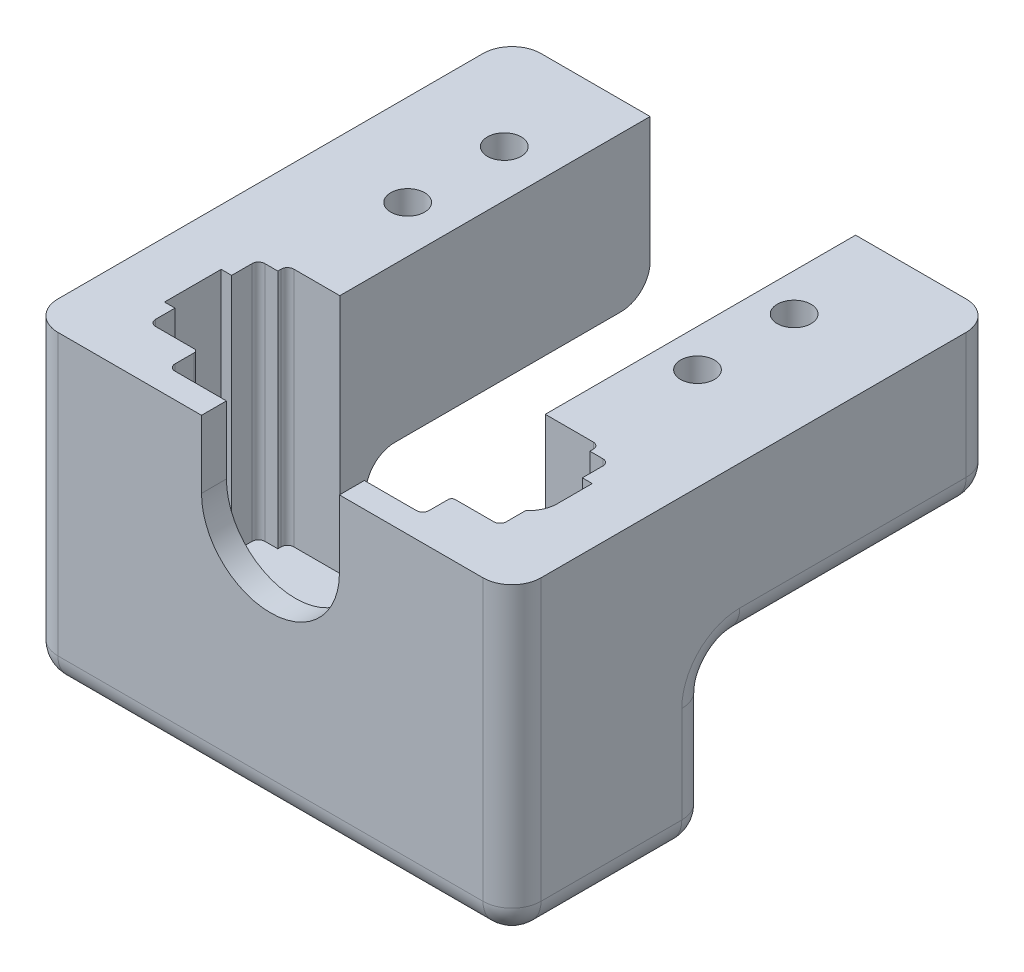
SolidWorks part; units mm, degrees
ref_plane "前视基准面" through (0, 0, 0) normal (0, 0, 1) x (1, 0, 0)
ref_plane "上视基准面" through (0, 0, 0) normal (0, 1, 0) x (1, 0, 0)
ref_plane "右视基准面" through (0, 0, 0) normal (1, 0, 0) x (0, 0, -1)
sketch "草图1" plane through (0, 0, 0) normal (0, 1, 0) x (1, 0, 0)
  line L1 (-25, -25) -> (25, -25)
  line L2 (-25, -25) -> (-25, 25)
  line L3 (-25, 25) -> (-11.2619, 25)
  line L4 (25, -25) -> (25, 25)
  line L5 (-6.2707, -6.2707) -> (25, 25) construction
  line L6 (-25, 25) -> (0, 0) construction
  line L7 (-18.1805, -10.8988) -> (-19.2049, -10.8988)
  line L10 (-15.4695, -7.1202) -> (-14.2003, -7.1202)
  line L11 (16.1805, -7.7702) -> (16.1805, -8.1202)
  line L12 (16.1805, -8.1202) -> (17.5305, -8.1202)
  line L13 (18.1805, -8.7702) -> (18.1805, -10.8988)
  line L14 (17.5305, -19.4202) -> (13.5305, -19.4202)
  line L24 (13.1805, -21.7702) -> (13.1805, -19.7702)
  line L25 (12.5305, -22.4202) -> (-12.4695, -22.4202)
  line L26 (-13.1195, -21.7702) -> (-13.1195, -19.7702)
  line L27 (-13.4695, -19.4202) -> (-17.4695, -19.4202)
  line L28 (-18.1195, -18.7702) -> (-18.1195, -16.7665)
  line L29 (-17.4695, -8.1202) -> (-16.1195, -8.1202)
  line L30 (-16.1195, -7.7702) -> (-16.1195, -8.1202)
  line L31 (18.1805, -10.8988) -> (19.2049, -10.8988)
  line L32 (19.2049, -10.8988) -> (19.2049, -16.7665)
  line L33 (19.2049, -16.7665) -> (18.1805, -16.7665)
  line L35 (0, -35.6784) -> (0, 5.6108) construction
  line L36 (-19.2049, -10.8988) -> (-19.2049, -16.7665)
  line L37 (-19.2049, -16.7665) -> (-18.1805, -16.7665)
  line L39 (-18.1805, -10.8988) -> (-18.1195, -10.8988)
  line L40 (-18.1805, -16.7665) -> (-18.1195, -16.7665)
  line L41 (18.1805, -16.7665) -> (18.1805, -18.7702)
  line L42 (-18.1195, -10.8988) -> (-18.1195, -8.7702)
  line L49 (7.1202, -7.1202) -> (25, -25) construction
  line L51 (12.5305, -7.1202) -> (15.5305, -7.1202)
  line L52 (12.5305, 25) -> (25, 25)
  line L53 (-14.2003, -7.1202) -> (-10.7032, -7.1202)
  line L54 (-10.7032, -7.1202) -> (-10.7032, 25)
  line L55 (-10.7032, 25) -> (-11.2619, 25)
  line L56 (12.5305, -7.1202) -> (10.5649, -7.1202)
  line L57 (10.5649, -7.1202) -> (10.5649, 25)
  line L58 (10.5649, 25) -> (12.5305, 25)
  arc A2 (16.1805, -7.7702) -> (15.5305, -7.1202) centre (15.5305, -7.7702) ccw
  arc A3 (18.1805, -8.7702) -> (17.5305, -8.1202) centre (17.5305, -8.7702) ccw
  arc A4 (17.5305, -19.4202) -> (18.1805, -18.7702) centre (17.5305, -18.7702) ccw
  arc A5 (13.5305, -19.4202) -> (13.1805, -19.7702) centre (13.5305, -19.7702) ccw
  arc A6 (12.5305, -22.4202) -> (13.1805, -21.7702) centre (12.5305, -21.7702) ccw
  arc A7 (-13.1195, -21.7702) -> (-12.4695, -22.4202) centre (-12.4695, -21.7702) ccw
  arc A8 (-13.1195, -19.7702) -> (-13.4695, -19.4202) centre (-13.4695, -19.7702) ccw
  arc A18 (-18.1195, -18.7702) -> (-17.4695, -19.4202) centre (-17.4695, -18.7702) ccw
  arc A19 (-17.4695, -8.1202) -> (-18.1195, -8.7702) centre (-17.4695, -8.7702) ccw
  arc A20 (-15.4695, -7.1202) -> (-16.1195, -7.7702) centre (-15.4695, -7.7702) ccw
  point P0 (0, 0)
  dimension "D1" = 50
  dimension "D2" = 50
extrude "凸台-拉伸1" add sketch "草图1" along normal blind 25
sketch "草图2" plane through (0, 0, 25) normal (0, 0, 1) x (1, 0, 0)
  line L4 (-25, 0) -> (25, 0)
  line L5 (25, 0) -> (25, 25)
  line L6 (25, 25) -> (-25, 25)
  line L7 (-25, 25) -> (-25, 0)
  line L8 (-25, 0) -> (25, 0)
  line L9 (25, 0) -> (25, 25)
  line L10 (25, 25) -> (-25, 25)
  line L11 (-25, 25) -> (-25, 0)
  arc A0 (-7.139, 25) -> (7.139, 25) centre (0, 25) ccw
  dimension "D1" = 0
extrude "切除-拉伸1" cut sketch "草图2" against normal blind 10 contours L10 A0 region at (0, 21.9701, 25)
sketch "草图5" plane through (0, 0, 0) normal (0, -1, 0) x (1, 0, 0)
  line L1 (-20.889, 4.4234) -> (20.889, 4.4234)
  line L2 (-20.889, 4.4234) -> (-20.889, 23.3182)
  line L3 (-20.889, 23.3182) -> (20.889, 23.3182)
  line L4 (20.889, 4.4234) -> (20.889, 23.3182)
  line L5 (-20.889, 4.4234) -> (20.889, 23.3182) construction
  line L6 (-20.889, 23.3182) -> (20.889, 4.4234) construction
  point P0 (0, 13.8708)
extrude "凸台-拉伸4" add sketch "草图5" against normal blind 7.1
sketch "草图6" plane through (0, 0, 0) normal (0, -1, 0) x (1, 0, 0)
  circle A4 centre (-15.551, -4.753) radius 1.75
  circle A5 centre (-15.551, -14.753) radius 1.75
  circle A6 centre (14.449, -4.753) radius 1.75
  circle A7 centre (14.449, -14.753) radius 1.75
  dimension "D1" = 3.5
  dimension "D2" = 3.5
  dimension "D3" = 3.5
  dimension "D4" = 3.5
extrude "切除-拉伸2" cut sketch "草图6" against normal through all
sketch "草图7" plane through (0, 0, 0) normal (0, -1, 0) x (1, 0, 0)
  line L0 (-10.7032, 4.4234) -> (-25, 4.4234)
  line L1 (-25, -25) -> (-25, 25) construction
  line L2 (-25, 4.4234) -> (-25, -26.3625)
  line L3 (-25, -26.3625) -> (26.9277, -26.3625)
  line L4 (26.9277, -26.3625) -> (26.9277, 4.4234)
  line L5 (26.9277, 4.4234) -> (-10.7032, 4.4234)
extrude "切除-拉伸3" cut sketch "草图7" against normal blind 16
fillet "圆角1" radius 3 13 edges at (25, 16, -10.2883) (-25, 16, -10.2883) (0, 0, 25) (25, 0, 14.7117) (0, 0, 4.4234) (-25, 0, 14.7117) (25, 12.5, 25) (19.2049, 16.05, 16.7665) (-25, 12.5, 25) (25, 8, 4.4234) (17.7824, 16, 4.4234) (-17.8516, 16, 4.4234) (-25, 8, 4.4234)
fillet "圆角3" radius 3 6 edges at (-16.3516, 16, -25) (-24.1213, 16.8787, -25) (16.2824, 16, -25) (24.1213, 16.8787, -25) (-25, 22, -25) (25, 22, -25)
sketch "草图8" plane through (0, 25, 0) normal (0, 1, 0) x (1, 0, 0)
  line L15 (25, -22) -> (25, 22)
  line L16 (22, 25) -> (10.5649, 25)
  line L17 (10.5649, 25) -> (10.5649, -7.1202)
  line L18 (10.5649, -7.1202) -> (15.5305, -7.1202)
  line L19 (16.1805, -7.7702) -> (16.1805, -8.1202)
  line L20 (16.1805, -8.1202) -> (17.5305, -8.1202)
  line L21 (18.1805, -8.7702) -> (18.1805, -10.8988)
  line L22 (18.1805, -10.8988) -> (19.2049, -10.8988)
  line L23 (19.2049, -10.8988) -> (19.2049, -14.5089)
  line L24 (18.1805, -16.7665) -> (18.1805, -18.7702)
  line L25 (17.5305, -19.4202) -> (13.5305, -19.4202)
  line L26 (13.1805, -19.7702) -> (13.1805, -21.7702)
  line L27 (12.5305, -22.4202) -> (7.139, -22.4202)
  line L28 (7.139, -22.4202) -> (7.139, -25)
  line L29 (7.139, -25) -> (22, -25)
  line L30 (25, -22) -> (25, 22)
  line L31 (22, 25) -> (10.5649, 25)
  line L32 (10.5649, 25) -> (10.5649, -7.1202)
  line L33 (10.5649, -7.1202) -> (15.5305, -7.1202)
  line L34 (16.1805, -7.7702) -> (16.1805, -8.1202)
  line L35 (16.1805, -8.1202) -> (17.5305, -8.1202)
  line L36 (18.1805, -8.7702) -> (18.1805, -10.8988)
  line L37 (18.1805, -10.8988) -> (19.2049, -10.8988)
  line L38 (19.2049, -10.8988) -> (19.2049, -14.5089)
  line L39 (18.1805, -16.7665) -> (18.1805, -18.7702)
  line L40 (17.5305, -19.4202) -> (13.5305, -19.4202)
  line L41 (13.1805, -19.7702) -> (13.1805, -21.7702)
  line L42 (12.5305, -22.4202) -> (7.139, -22.4202)
  line L43 (7.139, -22.4202) -> (7.139, -25)
  line L44 (7.139, -25) -> (22, -25)
  line L46 (-10.7032, 25) -> (-22, 25)
  line L47 (-25, 22) -> (-25, -22)
  line L48 (-22, -25) -> (-7.139, -25)
  line L49 (-7.139, -25) -> (-7.139, -22.4202)
  line L50 (-7.139, -22.4202) -> (-12.4695, -22.4202)
  line L51 (-13.1195, -21.7702) -> (-13.1195, -19.7702)
  line L52 (-13.4695, -19.4202) -> (-17.4695, -19.4202)
  line L53 (-18.1195, -18.7702) -> (-18.1195, -16.7665)
  line L54 (-18.1195, -16.7665) -> (-19.2049, -16.7665)
  line L55 (-19.2049, -16.7665) -> (-19.2049, -10.8988)
  line L56 (-19.2049, -10.8988) -> (-18.1195, -10.8988)
  line L57 (-18.1195, -10.8988) -> (-18.1195, -8.7702)
  line L58 (-17.4695, -8.1202) -> (-16.1195, -8.1202)
  line L59 (-16.1195, -8.1202) -> (-16.1195, -7.7702)
  line L60 (-15.4695, -7.1202) -> (-10.7032, -7.1202)
  line L61 (-10.7032, -7.1202) -> (-10.7032, 25)
  line L62 (-10.7032, 25) -> (-22, 25)
  line L63 (-25, 22) -> (-25, -22)
  line L64 (-22, -25) -> (-7.139, -25)
  line L65 (-7.139, -25) -> (-7.139, -22.4202)
  line L66 (-7.139, -22.4202) -> (-12.4695, -22.4202)
  line L67 (-13.1195, -21.7702) -> (-13.1195, -19.7702)
  line L68 (-13.4695, -19.4202) -> (-17.4695, -19.4202)
  line L69 (-18.1195, -18.7702) -> (-18.1195, -16.7665)
  line L70 (-18.1195, -16.7665) -> (-19.2049, -16.7665)
  line L71 (-19.2049, -16.7665) -> (-19.2049, -10.8988)
  line L72 (-19.2049, -10.8988) -> (-18.1195, -10.8988)
  line L73 (-18.1195, -10.8988) -> (-18.1195, -8.7702)
  line L74 (-17.4695, -8.1202) -> (-16.1195, -8.1202)
  line L75 (-16.1195, -8.1202) -> (-16.1195, -7.7702)
  line L76 (-15.4695, -7.1202) -> (-10.7032, -7.1202)
  line L77 (-10.7032, -7.1202) -> (-10.7032, 25)
  arc A7 (-22, 25) -> (-25, 22) centre (-22, 22) ccw
  arc A8 (25, 22) -> (22, 25) centre (22, 22) ccw
  arc A9 (16.1805, -7.7702) -> (15.5305, -7.1202) centre (15.5305, -7.7702) ccw
  arc A10 (18.1805, -8.7702) -> (17.5305, -8.1202) centre (17.5305, -8.7702) ccw
  arc A11 (18.1805, -16.7665) -> (19.2049, -14.5089) centre (16.2049, -14.5089) ccw
  arc A12 (17.5305, -19.4202) -> (18.1805, -18.7702) centre (17.5305, -18.7702) ccw
  arc A13 (13.5305, -19.4202) -> (13.1805, -19.7702) centre (13.5305, -19.7702) ccw
  arc A14 (12.5305, -22.4202) -> (13.1805, -21.7702) centre (12.5305, -21.7702) ccw
  arc A15 (22, -25) -> (25, -22) centre (22, -22) ccw
  arc A16 (25, 22) -> (22, 25) centre (22, 22) ccw
  arc A17 (16.1805, -7.7702) -> (15.5305, -7.1202) centre (15.5305, -7.7702) ccw
  arc A18 (18.1805, -8.7702) -> (17.5305, -8.1202) centre (17.5305, -8.7702) ccw
  arc A19 (18.1805, -16.7665) -> (19.2049, -14.5089) centre (16.2049, -14.5089) ccw
  arc A20 (17.5305, -19.4202) -> (18.1805, -18.7702) centre (17.5305, -18.7702) ccw
  arc A21 (13.5305, -19.4202) -> (13.1805, -19.7702) centre (13.5305, -19.7702) ccw
  arc A22 (12.5305, -22.4202) -> (13.1805, -21.7702) centre (12.5305, -21.7702) ccw
  arc A23 (22, -25) -> (25, -22) centre (22, -22) ccw
  arc A24 (-25, -22) -> (-22, -25) centre (-22, -22) ccw
  arc A25 (-13.1195, -21.7702) -> (-12.4695, -22.4202) centre (-12.4695, -21.7702) ccw
  arc A26 (-13.1195, -19.7702) -> (-13.4695, -19.4202) centre (-13.4695, -19.7702) ccw
  arc A27 (-18.1195, -18.7702) -> (-17.4695, -19.4202) centre (-17.4695, -18.7702) ccw
  arc A28 (-17.4695, -8.1202) -> (-18.1195, -8.7702) centre (-17.4695, -8.7702) ccw
  arc A29 (-15.4695, -7.1202) -> (-16.1195, -7.7702) centre (-15.4695, -7.7702) ccw
  arc A30 (-22, 25) -> (-25, 22) centre (-22, 22) ccw
  arc A31 (-25, -22) -> (-22, -25) centre (-22, -22) ccw
  arc A32 (-13.1195, -21.7702) -> (-12.4695, -22.4202) centre (-12.4695, -21.7702) ccw
  arc A33 (-13.1195, -19.7702) -> (-13.4695, -19.4202) centre (-13.4695, -19.7702) ccw
  arc A34 (-18.1195, -18.7702) -> (-17.4695, -19.4202) centre (-17.4695, -18.7702) ccw
  arc A35 (-17.4695, -8.1202) -> (-18.1195, -8.7702) centre (-17.4695, -8.7702) ccw
  arc A36 (-15.4695, -7.1202) -> (-16.1195, -7.7702) centre (-15.4695, -7.7702) ccw
  dimension "D1" = 0
  dimension "D2" = 0
extrude "凸台-拉伸5" add sketch "草图8" along normal blind 7
sketch "草图10" plane through (0, 32, 0) normal (0, 1, 0) x (1, 0, 0)
  circle A0 centre (-15.551, 4.753) radius 1.75 construction
  circle A1 centre (-15.551, 14.753) radius 1.75 construction
  circle A2 centre (-15.551, 4.753) radius 1.75
  circle A3 centre (-15.551, 14.753) radius 1.75
sketch "草图11" plane through (0, 32, 0) normal (0, 1, 0) x (1, 0, 0)
  circle A0 centre (14.449, 4.753) radius 1.75 construction
  circle A1 centre (14.449, 14.753) radius 1.75 construction
  circle A2 centre (14.449, 4.753) radius 1.75
  circle A3 centre (14.449, 14.753) radius 1.75
extrude "切除-拉伸4" cut sketch "草图11" against normal blind 17
extrude "切除-拉伸5" cut sketch "草图10" against normal blind 17
